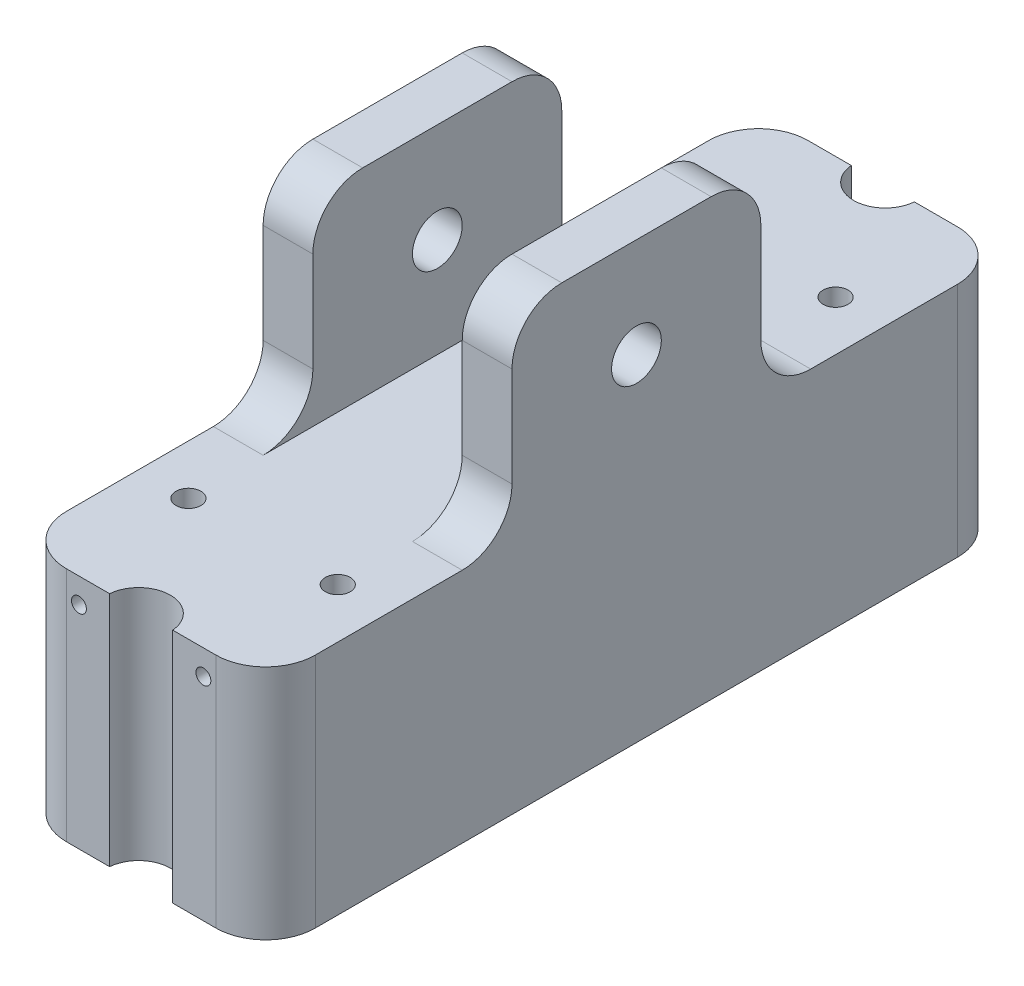
SolidWorks part; units mm, degrees
material "Nylon 101"
ref_plane "Front" through (0, 0, 0) normal (0, 0, 1) x (1, 0, 0)
ref_plane "Top" through (0, 0, 0) normal (0, 1, 0) x (1, 0, 0)
ref_plane "Right" through (0, 0, 0) normal (1, 0, 0) x (0, 0, -1)
sketch "Sketch1" plane through (0, 0, 0) normal (0, 1, 0) x (1, 0, 0)
  line L0 (-25, -75) -> (25, -75) construction
  line L1 (-15, 50) -> (15, 50) construction
  line L2 (0, -75) -> (0, 75) construction
  line L3 (-25, -75) -> (-25, 75)
  line L4 (25, -75) -> (25, 75)
  line L5 (25, 0) -> (0, 0) construction
  line L6 (25, 17) -> (97.2, 17)
  line L7 (25, 17) -> (25, -17)
  line L8 (25, -17) -> (97.2, -17)
  line L9 (97.2, 17) -> (97.2, -17)
  line L10 (-15, 50) -> (-15, -50) construction
  line L11 (-15, -50) -> (15, -50) construction
  line L12 (15, 50) -> (15, -50) construction
  line L13 (-25, -75.5) -> (25, -75.5)
  line L14 (-25, -74.5) -> (25, -74.5)
  line L15 (-25, 75.5) -> (25, 75.5)
  line L16 (-25, 74.5) -> (25, 74.5)
  circle A0 centre (0, 75) radius 6.35
  circle A1 centre (0, -75) radius 6.35
  arc A2 (-25, -75) -> (25, -75) centre (0, -75) ccw
  arc A3 (25, 75) -> (-25, 75) centre (0, 75) ccw
  circle A6 centre (-15, 50) radius 2.5
  circle A7 centre (-15, -50) radius 2.5
  circle A8 centre (15, -50) radius 2.5
  circle A9 centre (15, 50) radius 2.5
  point P8 (0, 0)
  point P24 (0, -50)
  dimension "D2" = 12.7
  dimension "D5" = 25
  dimension "D1" = 5
  dimension "D3" = 150
  dimension "D4" = 25
  dimension "D6" = 25
  dimension "D7" = 34
  dimension "D8" = 72.2
  dimension "D9" = 30
  dimension "D10" = 0.5
  dimension "D11" = 0.5
extrude "Boss-Extrude1" add sketch "Sketch1" along normal blind 10 and the other way blind 37.5 contours A1 L14 L4 L16 A0 L3 A9 A8 A7 A6 region at (0, 0, 0)
sketch "Sketch2" plane through (0, 0, 0) normal (0, 1, 0) x (1, 0, 0)
  line L0 (25, -75) -> (25, 75) construction
  line L1 (25, 25) -> (15, 25)
  line L2 (25, 25) -> (25, -25)
  line L3 (25, -25) -> (15, -25)
  line L4 (15, 25) -> (15, -25)
  line L6 (25, 0) -> (0, 0) construction
  line L7 (25, 0) -> (0, 0) construction
  line L8 (-25, -74.5) -> (-25, 74.5) construction
  line L9 (-25, 25) -> (-15, 25)
  line L10 (-25, 25) -> (-25, -25)
  line L11 (-25, -25) -> (-15, -25)
  line L12 (-15, 25) -> (-15, -25)
  line L13 (0, 0) -> (0, 4.5574) construction
  dimension "D1" = 50
  dimension "D2" = 10
extrude "Boss-Extrude2" add sketch "Sketch2" along normal blind 50
sketch "Sketch4" plane through (25, 0, 0) normal (1, 0, 0) x (0, 0, -1)
  line L0 (-25, 10) -> (25, 10) construction
  line L1 (-74.5, 10) -> (-25, 10) construction
  line L2 (-25, 50) -> (-25, 10) construction
  line L3 (0, 10) -> (0, 50) construction
  line L4 (-25, 50) -> (25, 50) construction
  circle A0 centre (0, 30) radius 5
  dimension "D1" = 10
extrude "Cut-Extrude2" cut sketch "Sketch4" against normal through all
fillet "Fillet1" radius 10 12 edges at (-20, 50, -25) (-20, 50, 25) (-20, 10, 25) (-20, 10, -25) (20, 50, -25) (20, 50, 25) (20, 10, 25) (20, 10, -25) (25, -13.75, -74.5) (-25, -13.75, -74.5) (-25, -13.75, 74.5) (25, -13.75, 74.5)
sketch "Sketch5" plane through (0, 0, 74.5) normal (0, 0, 1) x (1, 0, 0)
  line L0 (-12.5, 0) -> (-12.5, 10) construction
  line L1 (12.5, 10) -> (12.5, 0) construction
  line L2 (-15, 10) -> (-6.3303, 10) construction
  line L3 (6.3303, 10) -> (15, 10) construction
  line L4 (0, 0) -> (0, 2.4841) construction
  circle A0 centre (-12.5, 5) radius 1.5
  circle A1 centre (12.5, 5) radius 1.5
  dimension "D1" = 3
  dimension "D2" = 12.5
extrude "Cut-Extrude3" cut sketch "Sketch5" against normal blind 5
extrude "Cut-Extrude4" cut sketch "Sketch5<2>" along normal blind 5 from surface starting at face at (10.6651, -13.75, -74.5)
sketch "Sketch5<2>" plane through (0, 0, 74.5) normal (0, 0, 1) x (1, 0, 0) same geometry as "Sketch5"
